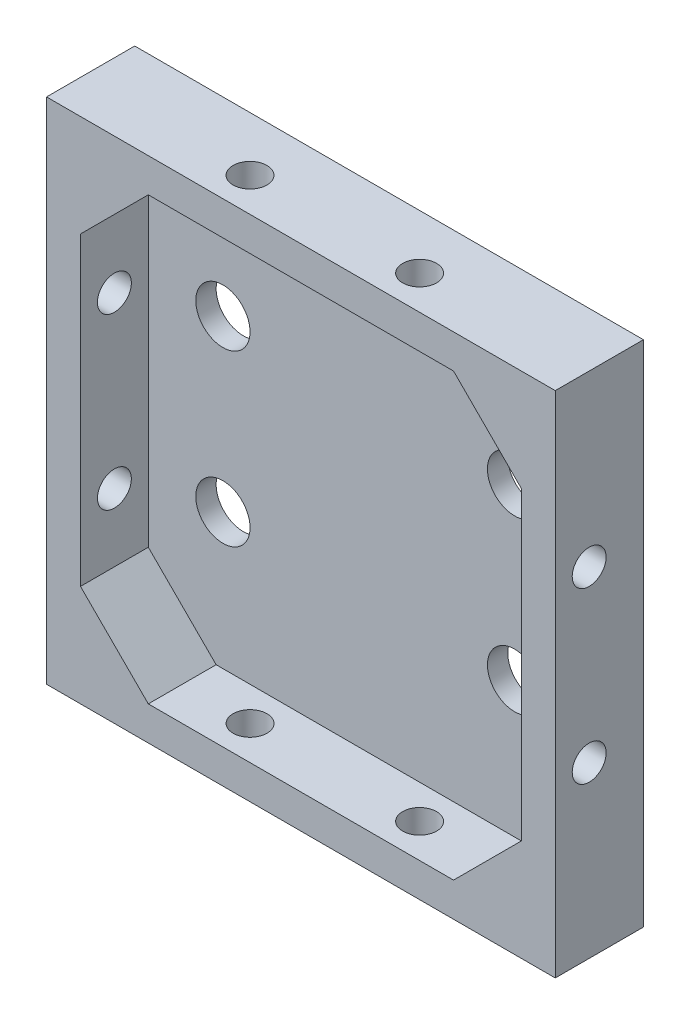
SolidWorks part; units mm, degrees
ref_plane "Plan de face" through (0, 0, 0) normal (0, 0, 1) x (1, 0, 0)
ref_plane "Plan de dessus" through (0, 0, 0) normal (0, 1, 0) x (1, 0, 0)
ref_plane "Plan de droite" through (0, 0, 0) normal (1, 0, 0) x (0, 0, -1)
sketch "Esquisse1" plane through (0, 0, 0) normal (0, 0, 1) x (1, 0, 0)
  line L0 (44.1184, 33.7284) -> (54.1184, 33.7284)
  line L1 (-20.8816, 33.7284) -> (44.1184, 33.7284)
  line L2 (-20.8816, 33.7284) -> (-20.8816, -41.2716)
  line L3 (-20.8816, -41.2716) -> (54.1184, -41.2716)
  line L4 (54.1184, 23.7284) -> (54.1184, -41.2716)
  line L5 (54.1184, 33.7284) -> (54.1184, 23.7284)
  point P6 (54.1184, 33.7284)
  dimension "D1" = 75
  dimension "D2" = 75
extrude "Boss.-Extru.1" add sketch "Esquisse1" along normal blind 13
shell "Coque1" thickness 5 removed face at (16.6184, -3.7716, 13)
sketch "Esquisse2" plane through (-20.8816, 0, 0) normal (-1, 0, 0) x (0, 0, 1)
  line L0 (13, 33.7284) -> (13, -41.2716) construction
  line L1 (13, 33.7284) -> (0, 33.7284) construction
  line L2 (13, -41.2716) -> (0, -41.2716) construction
  circle A0 centre (8, 8.7284) radius 2.5
  circle A1 centre (8, -16.2716) radius 2.5
  dimension "D1" = 5
  dimension "D2" = 5
  dimension "D3" = 5
  dimension "D4" = 5
  dimension "D5" = 25
  dimension "D6" = 25
extrude "Enlèv. mat.-Extru.1" cut sketch "Esquisse2" against normal up to surface (75 mm away) contours A1 | A0 region at (-20.8816, -16.2716, 8) up to face at (54.1184, -3.7716, 6.5)
sketch "Esquisse3" plane through (0, -41.2716, 0) normal (0, -1, 0) x (1, 0, 0)
  line L0 (-20.8816, 13) -> (54.1184, 13) construction
  line L2 (54.1184, 13) -> (54.1184, 0) construction
  line L3 (-20.8816, 13) -> (-20.8816, 0) construction
  circle A0 centre (4.1184, 8) radius 2.5
  circle A1 centre (29.1184, 8) radius 2.5
  dimension "D1" = 5
  dimension "D2" = 5
  dimension "D3" = 5
  dimension "D4" = 5
  dimension "D5" = 25
  dimension "D6" = 25
extrude "Enlèv. mat.-Extru.2" cut sketch "Esquisse3" against normal up to surface (75 mm away) up to face at (16.6184, 33.7284, 6.5)
sketch "Esquisse4" plane through (0, 0, 3) normal (0, 0, 1) x (1, 0, 0)
  line L0 (-5.8816, 28.7284) -> (-15.8816, 18.7284)
  line L1 (49.1184, 28.7284) -> (-15.8816, 28.7284) construction
  line L2 (-15.8816, 28.7284) -> (-15.8816, -36.2716) construction
  line L3 (-15.8816, 18.7284) -> (-15.8816, 28.7284)
  line L4 (-15.8816, 28.7284) -> (-5.8816, 28.7284)
  line L5 (49.1184, 28.7284) -> (49.1184, 18.7284)
  line L6 (49.1184, -36.2716) -> (49.1184, 28.7284) construction
  line L7 (49.1184, 18.7284) -> (39.1184, 28.7284)
  line L8 (39.1184, 28.7284) -> (49.1184, 28.7284)
  line L9 (49.1184, 28.7284) -> (-15.8816, 28.7284) construction
  line L10 (49.1184, -36.2716) -> (49.1184, -26.2716)
  line L11 (49.1184, -26.2716) -> (39.1184, -36.2716)
  line L12 (-15.8816, -36.2716) -> (49.1184, -36.2716) construction
  line L13 (39.1184, -36.2716) -> (49.1184, -36.2716)
  line L14 (-5.8816, -36.2716) -> (-15.8816, -26.2716)
  line L15 (-15.8816, 28.7284) -> (-15.8816, -36.2716) construction
  line L16 (-15.8816, -26.2716) -> (-15.8816, -36.2716)
  line L17 (-15.8816, -36.2716) -> (-5.8816, -36.2716)
  dimension "D1" = 10
  dimension "D2" = 10
  dimension "D3" = 10
  dimension "D4" = 10
  dimension "D5" = 10
  dimension "D6" = 10
  dimension "D7" = 10
  dimension "D8" = 10
extrude "Boss.-Extru.2" add sketch "Esquisse4" along normal up to surface (10 mm away) up to face at (16.6184, -3.7716, 13)
sketch "Esquisse5" plane through (0, 0, 3) normal (0, 0, 1) x (1, 0, 0)
  line L0 (54.1184, 33.7284) -> (-20.8816, 33.7284) construction
  line L2 (-20.8816, 33.7284) -> (-20.8816, -41.2716) construction
  circle A0 centre (-4.8816, 8.7284) radius 4
  dimension "D1" = 8
  dimension "D4" = 25
  dimension "D6" = 16
extrude "Enlèv. mat.-Extru.3" cut sketch "Esquisse5" against normal up to surface (3 mm away) up to face at (16.6184, -3.7716, 0)
pattern_linear "Répétition linéaire1" count 2 spacing 43 along (1, 0, 0) count 2 spacing 25 along (0, -1, 0) of "Enlèv. mat.-Extru.3"
